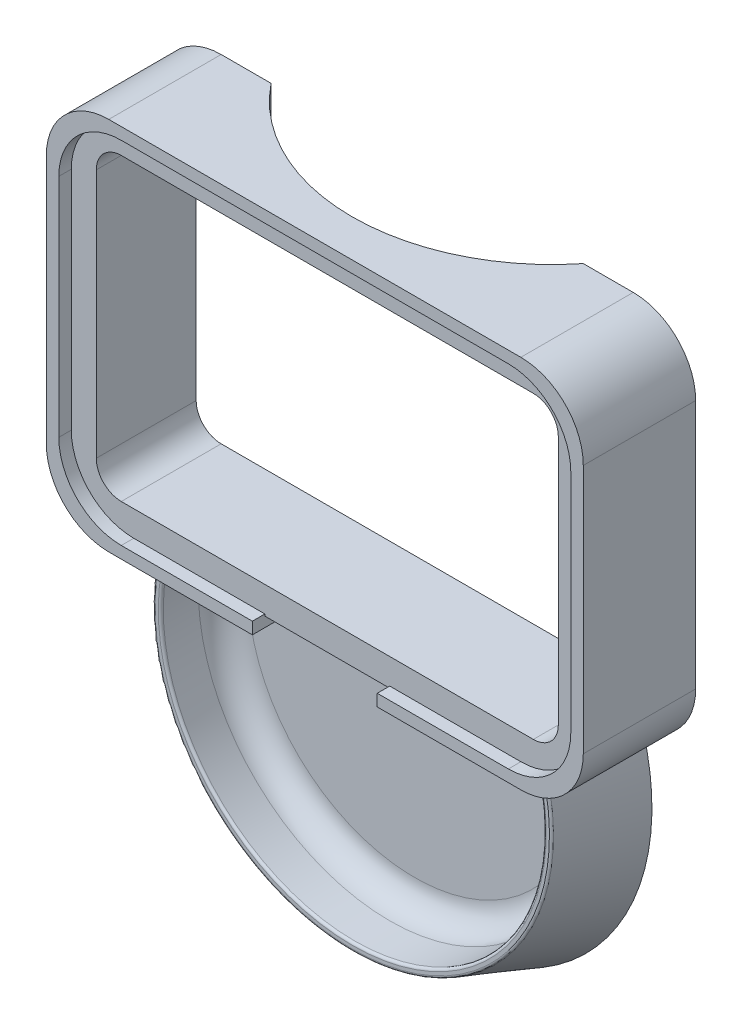
SolidWorks part; units mm, degrees
ref_plane "Front Plane" through (0, 0, 0) normal (0, 0, 1) x (1, 0, 0)
ref_plane "Top Plane" through (0, 0, 0) normal (0, 1, 0) x (1, 0, 0)
ref_plane "Right Plane" through (0, 0, 0) normal (1, 0, 0) x (0, 0, -1)
sketch "Sketch1" plane through (0, 0, 0) normal (0, 0, 1) x (1, 0, 0)
  line L0 (-82.5, 60) -> (82.5, 60)
  line L1 (-82.5, 75) -> (82.5, 75)
  line L2 (-107.5, 50) -> (-107.5, -50)
  line L3 (-82.5, -75) -> (82.5, -75)
  line L4 (107.5, 50) -> (107.5, -50)
  line L5 (-107.5, 75) -> (107.5, -75) construction
  line L6 (-107.5, -75) -> (107.5, 75) construction
  line L7 (92.5, 50) -> (92.5, -50)
  line L8 (-82.5, -60) -> (82.5, -60)
  line L9 (-92.5, 50) -> (-92.5, -50)
  arc A0 (-107.5, -50) -> (-82.5, -75) centre (-82.5, -50) ccw
  arc A1 (82.5, -75) -> (107.5, -50) centre (82.5, -50) ccw
  arc A2 (82.5, 75) -> (107.5, 50) centre (82.5, 50) cw
  arc A3 (-82.5, 75) -> (-107.5, 50) centre (-82.5, 50) ccw
  arc A4 (82.5, 60) -> (92.5, 50) centre (82.5, 50) cw
  arc A5 (82.5, -60) -> (92.5, -50) centre (82.5, -50) ccw
  arc A6 (-92.5, -50) -> (-82.5, -60) centre (-82.5, -50) ccw
  arc A7 (-82.5, 60) -> (-92.5, 50) centre (-82.5, 50) ccw
  point P0 (0, 0)
  dimension "D3" = 25
  dimension "D1" = 215
  dimension "D2" = 150
  dimension "D4" = 15
extrude "Boss-Extrude1" add sketch "Sketch1" along normal blind 45
sketch "Sketch2" plane through (0, 0, 45) normal (0, 0, 1) x (1, 0, 0)
  line L1 (-77.5, -70.25) -> (77.5, -70.25)
  line L2 (-102.5, -45.25) -> (-102.5, 45.25)
  line L3 (-77.5, 70.25) -> (77.5, 70.25)
  line L4 (102.5, -45.25) -> (102.5, 45.25)
  line L5 (-102.5, -70.25) -> (102.5, 70.25) construction
  line L6 (-102.5, 70.25) -> (102.5, -70.25) construction
  arc A0 (-77.5, -70.25) -> (-102.5, -45.25) centre (-77.5, -45.25) cw
  arc A1 (77.5, -70.25) -> (102.5, -45.25) centre (77.5, -45.25) ccw
  arc A2 (77.5, 70.25) -> (102.5, 45.25) centre (77.5, 45.25) cw
  arc A3 (-102.5, 45.25) -> (-77.5, 70.25) centre (-77.5, 45.25) cw
  point P0 (0, 0)
  dimension "D3" = 25
  dimension "D1" = 205
  dimension "D2" = 140.5
extrude "Cut-Extrude1" cut sketch "Sketch2" against normal blind 5
sketch "Sketch3" plane through (0, 0, 0) normal (0, 0, 1) x (1, 0, 0)
  line L0 (0, 0) -> (0, -100) construction
  line L1 (-80.6226, -60) -> (80.6226, -60)
  line L2 (82.5, -60) -> (-82.5, -60) construction
  arc A0 (-80.6226, -60) -> (80.6226, -60) centre (0, -100) ccw
  dimension "D1" = 180
  dimension "D2" = 100
extrude "Boss-Extrude2" add sketch "Sketch3" along normal blind 30 draft 19
sketch "Sketch4" plane through (0, 0, 30) normal (0, 0, 1) x (1, 0, 0)
  line L0 (-73.446, -78) -> (73.446, -78)
  line L1 (-75.6461, -75) -> (75.6461, -75) construction
  arc A3 (-72.7977, -75.9414) -> (72.7977, -75.9414) centre (0, -100) ccw
  arc A4 (-73.446, -78) -> (73.446, -78) centre (0, -100) ccw
  dimension "D2" = 3
  dimension "D1" = 3
extrude "Cut-Extrude2" cut sketch "Sketch4" against normal blind 25
sketch "Sketch5" plane through (0, 0, 45) normal (0, 0, 1) x (1, 0, 0)
  line L0 (73.446, -78) -> (-73.446, -78) construction
  line L1 (-25, -70.2154) -> (25, -70.2154)
  line L2 (-25, -70.2154) -> (-25, -85.7846)
  line L3 (-25, -85.7846) -> (25, -85.7846)
  line L4 (25, -70.2154) -> (25, -85.7846)
  line L5 (-25, -70.2154) -> (25, -85.7846) construction
  line L6 (-25, -85.7846) -> (25, -70.2154) construction
  point P0 (0, -78)
  dimension "D1" = 50
extrude "Cut-Extrude3" cut sketch "Sketch5" against normal blind 5
chamfer "Chamfer1" distance 4 angle 45 2 edges at (0, -75, 30) (0, -75, 40)
sketch "Sketch6" plane through (0, 75, 0) normal (0, 1, 0) x (1, 0, 0)
  line L0 (82.5, 0) -> (-82.5, 0) construction
  line L1 (62.5, 0) -> (-62.5, 0)
  arc A0 (-62.5, 0) -> (62.5, 0) centre (0, 49.9375) ccw
  dimension "D3" = 80
  dimension "D1" = 20
  dimension "D2" = 20
extrude "Cut-Extrude4" cut sketch "Sketch6" against normal blind 25
fillet "Fillet1" radius 10 2 edges at (0, -78, 5) (0, -176.6702, 5)
fillet "Fillet2" radius 1 8 edges at (-73.5938, -78.4995, 30.5005) (-75.5468, -76.9824, 32.0176) (73.5938, -78.4995, 30.5005) (75.5468, -76.9824, 32.0176) (-75.2954, -79, 30) (0, -176.6702, 30) (75.2954, -79, 30) (0, -179.6702, 30)
